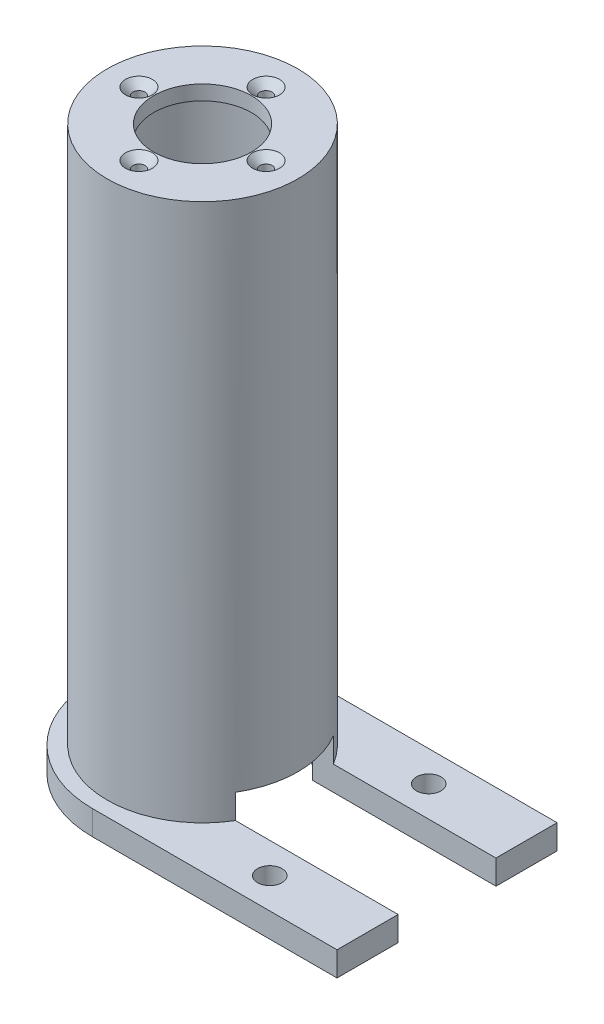
SolidWorks part; units mm, degrees
material "3003 Alloy"
ref_plane "Front Plane" through (0, 0, 0) normal (0, 0, 1) x (1, 0, 0)
ref_plane "Top Plane" through (0, 0, 0) normal (0, 1, 0) x (1, 0, 0)
ref_plane "Right Plane" through (0, 0, 0) normal (1, 0, 0) x (0, 0, -1)
ref_axis "Axis1" through (53.75, 0, 0) along (-1, 0, 0)
sketch "Sketch1" plane through (0, 0, 0) normal (0, 1, 0) x (1, 0, 0)
  circle A0 centre (0, 0) radius 19.5
  dimension "D1" = 39
sketch "Sketch2" plane through (0, 0, 0) normal (0, 1, 0) x (1, 0, 0)
  circle A0 centre (0, 0) radius 16
  dimension "D1" = 32
extrude "OuterDiameterStock" add sketch "Sketch1" against normal blind 115
sketch "Sketch4" plane through (0, 0, 0) normal (0, 1, 0) x (1, 0, 0)
  line L1 (0, 22.5) -> (50, 22.5)
  line L3 (0, -22.5) -> (50, -22.5)
  line L4 (50, 22.5) -> (50, -22.5)
  arc A0 (0, 22.5) -> (0, -22.5) centre (0, 0) ccw
  dimension "D1" = 45
  dimension "D2" = 50
extrude "ScrewOnBase" add sketch "Sketch4" along normal blind 5 from surface starting at face at (0, -115, 19.5)
extrude "InnerDiameter" cut sketch "Sketch2" against normal through all from offset 3 offset against normal yes
sketch "Sketch3" plane through (0, 0, 0) normal (0, 1, 0) x (1, 0, 0)
  circle A0 centre (0, 0) radius 10
  dimension "D1" = 20
extrude "Hole" cut sketch "Sketch3" against normal through all
sketch "Sketch5" plane through (0, 0, 0) normal (0, 1, 0) x (1, 0, 0)
  line L0 (0, 0) -> (0, 13) construction
  line L1 (0, 0) -> (13, 0) construction
  line L2 (0, 0) -> (0, -13) construction
  line L3 (0, 0) -> (-13, 0) construction
  circle A0 centre (0, 13) radius 1.25
  circle A1 centre (13, 0) radius 1.25
  circle A2 centre (0, -13) radius 1.25
  circle A3 centre (-13, 0) radius 1.25
  point P13 (0, 0)
  dimension "D1" = 2.5
  dimension "D2" = 13
  dimension "D3" = 4
extrude "Cut-Extrude3" cut sketch "Sketch5" against normal up to next
chamfer "Chamfer1" distance 1.5 angle 45 4 edges at (0, 0, 14.25) (13, 0, 1.25) (0, 0, -11.75) (-13, 0, 1.25)
sketch "Sketch6" plane through (0, 0, 0) normal (0, 1, 0) x (1, 0, 0)
  line L0 (50, -22.5) -> (50, 22.5) construction
  line L1 (0, -10) -> (50, -10)
  line L2 (0, -10) -> (0, 10)
  line L3 (0, 10) -> (50, 10)
  line L4 (50, -10) -> (50, 10)
  point P4 (0, 0)
  dimension "D1" = 20
extrude "WireSlot" cut sketch "Sketch6" along normal offset from surface (10 mm away) 5 from surface up to face at (0, -110, 19.5) offset beyond the face yes starting at face at (0, -115, 16)
sketch "Sketch7" plane through (0, 0, 0) normal (0, 1, 0) x (1, 0, 0)
  line L0 (30, 22.5) -> (30, 10) construction
  line L1 (50, 22.5) -> (0, 22.5) construction
  line L2 (16.7407, 10) -> (50, 10) construction
  line L3 (-39.875, 0) -> (39.875, 0) construction
  line L4 (30, -22.5) -> (30, -10) construction
  line L5 (-18.5862, 25) -> (58.8955, 25) construction
  circle A0 centre (30, 16.25) radius 2.5
  circle A1 centre (30, -16.25) radius 2.5
  point P9 (30, 16.25)
  dimension "D1" = 5
  dimension "D2" = 30
  dimension "D3" = 2.5
  dimension "D4" = 8.75
extrude "Mounting Holes" cut sketch "Sketch7" along normal up to next and the other way through all from surface starting at face at (21.7487, -115, 0)
